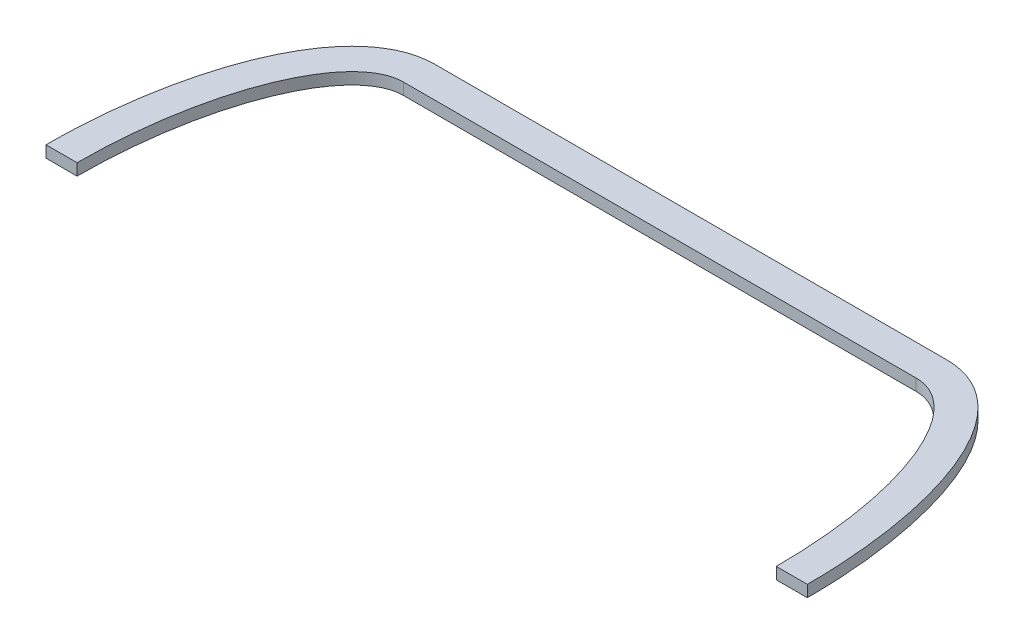
SolidWorks part; units mm, degrees
ref_plane "Front Plane" through (0, 0, 0) normal (0, 0, 1) x (1, 0, 0)
ref_plane "Top Plane" through (0, 0, 0) normal (0, 1, 0) x (1, 0, 0)
ref_plane "Right Plane" through (0, 0, 0) normal (1, 0, 0) x (0, 0, -1)
sketch "Sketch1" plane through (0, 0, 0) normal (0, 1, 0) x (1, 0, 0)
  line L0 (33, 30) -> (-33, -30) construction
  line L1 (-33, 30) -> (33, 30)
  line L2 (-33, 30) -> (-33, -30) construction
  line L3 (-33, -30) -> (33, -30)
  line L4 (33, 30) -> (33, -30) construction
  line L5 (-33, 30) -> (33, -30) construction
  line L6 (0, 30) -> (0, -30) construction
  ellipse E0 centre (-33, 0) end of major axis (-33, -30) minor radius 12 (-33, 30) -> (-33, -30) ccw
  ellipse E1 centre (33, 0) end of major axis (33, 30) minor radius 12 (33, 30) -> (33, -30) cw
  point P20 (0, 0)
  dimension "D1" = 66
  dimension "D2" = 60
  dimension "D3" = 12
extrude "Boss-Extrude1" add sketch "Sketch1" along normal blind 1.5 contours L1 E1 L3 E0
shell "Shell1" thickness 4 removed face at (0, 0, 0) removed face at (0, 1.5, 0) outward yes
sketch "Sketch2" plane through (0, 0, 0) normal (0, 1, 0) x (1, 0, 0)
  line L1 (-53.1803, 0) -> (55.7581, 0)
  line L2 (-53.1803, 0) -> (-53.1803, -37.45)
  line L3 (-53.1803, -37.45) -> (55.7581, -37.45)
  line L4 (55.7581, 0) -> (55.7581, -37.45)
extrude "Cut-Extrude2" cut sketch "Sketch2" along normal through all
